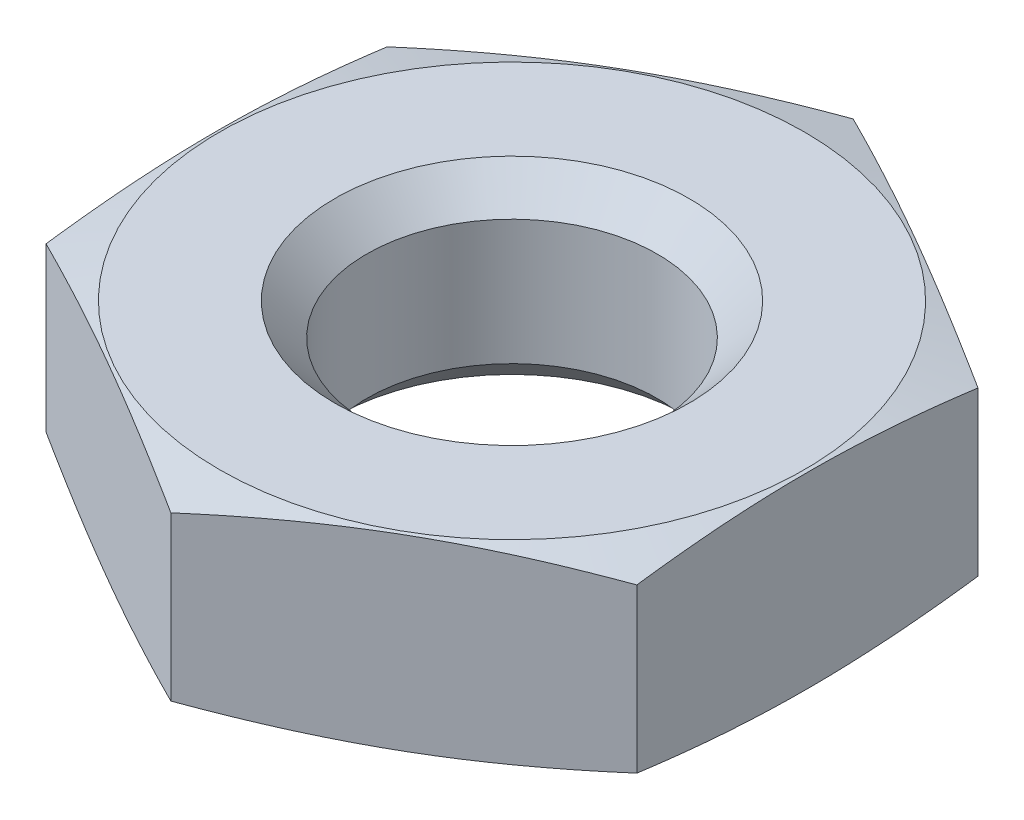
SolidWorks part; units mm, degrees
ref_plane "Ebene vorne" through (0, 0, 0) normal (0, 0, 1) x (1, 0, 0)
ref_plane "Ebene oben" through (0, 0, 0) normal (0, 1, 0) x (1, 0, 0)
ref_plane "Ebene rechts" through (0, 0, 0) normal (1, 0, 0) x (0, 0, -1)
sketch "Skizze1" plane through (0, 0, 0) normal (0, 0, 1) x (1, 0, 0)
  line L0 (0, 0) -> (4.95, 0)
  line L1 (4.95, 0) -> (10.9213, -1.6)
  line L2 (10.9213, -1.6) -> (4.95, -3.2)
  line L3 (4.95, -3.2) -> (0, -3.2)
  line L4 (0, -3.2) -> (0, 0)
  line L5 (0, -3.2) -> (0, 0) construction
revolve "Rotation1" add sketch "Skizze1" angle 360 about L5
sketch "Skizze2" plane through (0, 0, 0) normal (0, 1, 0) x (1, 0, 0)
  line L0 (-20, 20) -> (-20, -20)
  line L1 (-20, -20) -> (20, -20)
  line L2 (20, -20) -> (20, 20)
  line L3 (20, 20) -> (-20, 20)
  line L4 (-5, -2.8868) -> (0, -5.7735)
  line L5 (0, -5.7735) -> (5, -2.8868)
  line L6 (5, -2.8868) -> (5, 2.8868)
  line L7 (5, 2.8868) -> (0, 5.7735)
  line L8 (0, 5.7735) -> (-5, 2.8868)
  line L9 (-5, 2.8868) -> (-5, -2.8868)
extrude "Schnitt-Linear austragen1" cut sketch "Skizze2" along normal blind 4.2 and the other way blind 4.2
sketch "Skizze3" plane through (0, 0, 0) normal (0, 0, 1) x (1, 0, 0)
  line L0 (0, 0) -> (3, 0)
  line L1 (3, 0) -> (2.4585, -0.5415)
  line L2 (2.4585, -0.5415) -> (2.4585, -2.6585)
  line L3 (2.4585, -2.6585) -> (3, -3.2)
  line L4 (3, -3.2) -> (0, -3.2)
  line L5 (0, -3.2) -> (0, 0)
  line L6 (0, -3.2) -> (0, 0) construction
revolve "Schnitt-Rotation1" cut sketch "Skizze3" angle 360 about L6 reverse direction yes
cosmetic thread "Gewindedarstellung1" parameters "D1"=3.2, "D2"=6
ref_plane "Ebene1" through (0, -1.6, 0) normal (0, 1, 0) x (1, 0, 0)
ref_plane "2CYL XY" through (0, -1.6, 0) normal (0, 1, 0) x (1, 0, 0)
ref_plane "2CYL XZ" through (0, 0, 0) normal (0, 0, 1) x (1, 0, 0)
ref_plane "2CYL YZ" through (0, 0, 0) normal (1, 0, 0) x (0, 0, -1)
ref_axis "2CYL X" through (-80.9, -1.6, 0) along (1, 0, 0)
ref_axis "2CYL Y" through (0, -1.6, 50) along (0, 0, -1)
ref_axis "2CYL Z" through (0, 50, 0) along (0, -1, 0)
sketch3d "2CYL"
  point P0 (0, -1.6, 0)
ref_plane "din439b_punkt XY" through (0, 0, 0) normal (0, 1, 0) x (1, 0, 0)
ref_plane "din439b_punkt XZ" through (0, 0, 0) normal (0, 0, 1) x (1, 0, 0)
ref_plane "din439b_punkt YZ" through (0, 0, 0) normal (1, 0, 0) x (0, 0, -1)
ref_axis "din439b_punkt X" through (-80.9, 0, 0) along (1, 0, 0)
ref_axis "din439b_punkt Y" through (0, 0, 50) along (0, 0, -1)
ref_axis "din439b_punkt Z" through (0, 50, 0) along (0, -1, 0)
sketch3d "din439b_punkt"
  point P0 (0, 0, 0)
